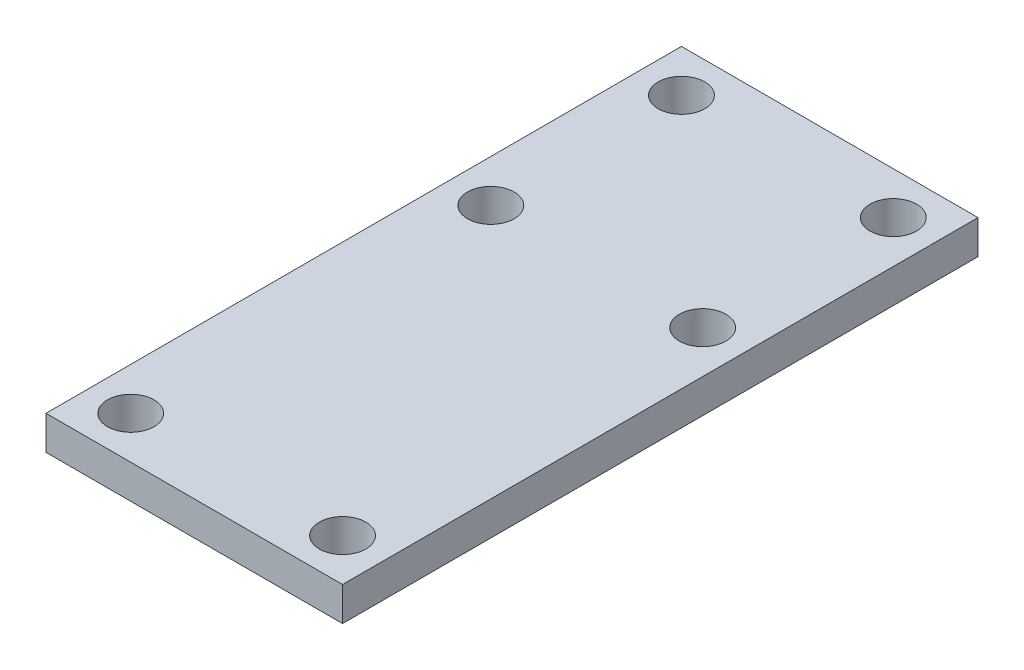
SolidWorks part; units mm, degrees
ref_plane "Front Plane" through (0, 0, 0) normal (0, 0, 1) x (1, 0, 0)
ref_plane "Top Plane" through (0, 0, 0) normal (0, 1, 0) x (1, 0, 0)
ref_plane "Right Plane" through (0, 0, 0) normal (1, 0, 0) x (0, 0, -1)
sketch "Sketch1" plane through (0, 0, 0) normal (0, 1, 0) x (1, 0, 0)
  line L0 (-7, 15) -> (7, -15) construction
  line L1 (-7, 15) -> (7, 15)
  line L2 (-7, 15) -> (-7, -15)
  line L3 (-7, -15) -> (7, -15)
  line L4 (7, 15) -> (7, -15)
  point P4 (0, 0)
  dimension "D1" = 30
  dimension "D2" = 14
extrude "Boss-Extrude1" add sketch "Sketch1" along normal blind 1.6
hole_wizard "M2 Clearance Hole1" positions "Sketch2" profile "Sketch3" hole size "M2" standard "ANSI Metric"
sketch "Sketch2" plane through (0, 1.6, 0) normal (0, 1, 0) x (1, 0, 0)
  line L0 (-7, 15) -> (-7, -15) construction
  line L1 (0, 15) -> (0, -15) construction
  line L2 (7, 15) -> (-7, 15) construction
  line L3 (-7, -15) -> (7, -15) construction
  line L5 (-5, 13) -> (-5, 15) construction
  line L7 (-5, -13) -> (-5, -15) construction
  point P0 (-5, 13)
  point P2 (-5, 4)
  point P4 (-5, -13)
  point P27 (5, -13)
  point P28 (5, 4)
  point P29 (5, 13)
  dimension "D1" = 2
  dimension "D2" = 2
  dimension "D3" = 9
sketch "Sketch3" plane through (-5, 1.6, -13) normal (1, 0, 0) x (0, 0, 1)
  line L0 (0, 0) -> (0, 5.8609)
  line L1 (0, 5.8609) -> (1.1, 5.2)
  line L2 (1.1, 5.2) -> (1.1, 0)
  line L5 (1.1, 0) -> (0, 0)
  line L10 (0, 5.8609) -> (-1.1, 5.2) construction
  line L11 (0, -6.35) -> (0, 107.95) construction
  dimension "Hole Dia." = 2.2
  dimension "Hole Depth" = 5.2
  dimension "Drill Angle" = 118
mirror "Mirror1" [suppressed] about plane through (0, 0, 0) normal (1, 0, 0)
sketch "Sketch4" plane through (0, 0, 0) normal (0, -1, 0) x (1, 0, 0)
  circle A0 centre (0, -12) radius 0.75 construction
  circle A1 centre (0, -12) radius 0.75
sketch "Sketch5" plane through (0, 0, 0) normal (0, -1, 0) x (1, 0, 0)
  line L12 (7, 15) -> (3, 15)
  line L13 (7, -15) -> (7, 15)
  line L14 (3, -15) -> (7, -15)
  line L15 (3, -9.5) -> (3, -15)
  line L16 (-0.5, -7) -> (0.5, -7)
  line L17 (-3, -15) -> (-3, -9.5)
  line L18 (-7, -15) -> (-3, -15)
  line L19 (-7, 15) -> (-7, -15)
  line L20 (-3, 15) -> (-7, 15)
  line L21 (-3, 2.5) -> (-3, 15)
  line L22 (0.5, 0) -> (-0.5, 0)
  line L23 (3, 15) -> (3, 2.5)
  line L24 (7, 15) -> (3, 15)
  line L25 (7, -15) -> (7, 15)
  line L26 (3, -15) -> (7, -15)
  line L27 (3, -9.5) -> (3, -15)
  line L28 (-0.5, -7) -> (0.5, -7)
  line L29 (-3, -15) -> (-3, -9.5)
  line L30 (-7, -15) -> (-3, -15)
  line L31 (-7, 15) -> (-7, -15)
  line L32 (-3, 15) -> (-7, 15)
  line L33 (-3, 2.5) -> (-3, 15)
  line L34 (0.5, 0) -> (-0.5, 0)
  line L35 (3, 15) -> (3, 2.5)
  arc A4 (3, -9.5) -> (0.5, -7) centre (0.5, -9.5) ccw
  arc A5 (-0.5, -7) -> (-3, -9.5) centre (-0.5, -9.5) ccw
  arc A6 (-3, 2.5) -> (-0.5, 0) centre (-0.5, 2.5) ccw
  arc A7 (0.5, 0) -> (3, 2.5) centre (0.5, 2.5) ccw
  arc A8 (3, -9.5) -> (0.5, -7) centre (0.5, -9.5) ccw
  arc A9 (-0.5, -7) -> (-3, -9.5) centre (-0.5, -9.5) ccw
  arc A10 (-3, 2.5) -> (-0.5, 0) centre (-0.5, 2.5) ccw
  arc A11 (0.5, 0) -> (3, 2.5) centre (0.5, 2.5) ccw
  dimension "D1" = 0
extrude "Cut-Extrude3" cut sketch "Sketch5" against normal blind 0.001
